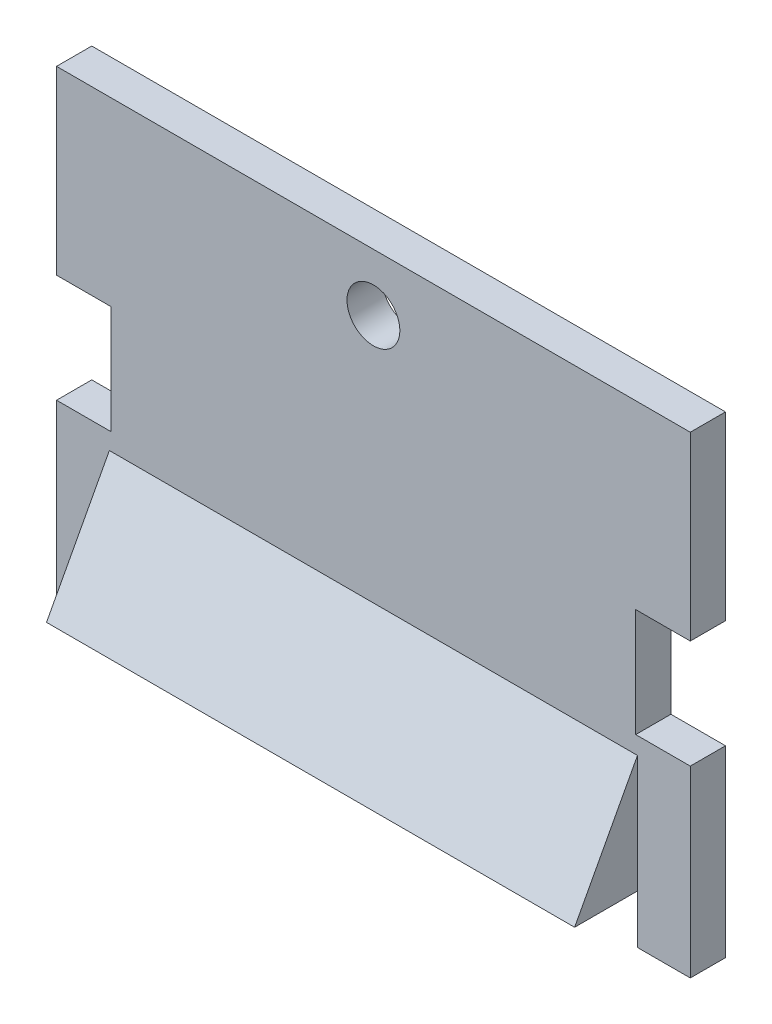
SolidWorks part; units mm, degrees
ref_plane "Front Plane" through (0, 0, 0) normal (0, 0, 1) x (1, 0, 0)
ref_plane "Top Plane" through (0, 0, 0) normal (0, 1, 0) x (1, 0, 0)
ref_plane "Right Plane" through (0, 0, 0) normal (1, 0, 0) x (0, 0, -1)
sketch "Sketch1" plane through (0, 0, 0) normal (1, 0, 0) x (0, 0, -1)
  line L0 (0, 0) -> (0, 26.85)
  line L1 (0, 26.85) -> (-2, 26.85)
  line L2 (-2, 26.85) -> (-2, 9.45)
  line L3 (-2, 9.45) -> (-5.57, 2.78)
  line L4 (-5.57, 2.78) -> (-2, 2.78)
  line L5 (-2, 2.78) -> (-2, 0)
  line L6 (-2, 0) -> (0, 0)
  dimension "D1" = 2
  dimension "D2" = 26.85
  dimension "D3" = 2.78
  dimension "D4" = 3.57
  dimension "D5" = 17.4
extrude "Boss-Extrude1" add sketch "Sketch1" along normal mid plane 36
sketch "Sketch2" plane through (0, 0, 0) normal (0, 0, -1) x (-1, 0, 0)
  line L0 (-18, 0) -> (18, 0) construction
  line L1 (-15, 0) -> (15, 0)
  line L2 (-15, 0) -> (-15, 2.78)
  line L3 (-15, 2.78) -> (15, 2.78)
  line L4 (15, 0) -> (15, 2.78)
  line L5 (-18, 2.78) -> (18, 2.78) construction
  line L6 (-18, 26.85) -> (18, 26.85) construction
  circle A0 centre (0, 23.6) radius 1.5
  point P6 (0, 2.78)
  dimension "D2" = 3
  dimension "D1" = 30
  dimension "D3" = 3.25
extrude "Cut-Extrude1" cut sketch "Sketch2" against normal through all
sketch "Sketch3" plane through (0, 0, 0) normal (0, 0, -1) x (-1, 0, 0)
  line L0 (-18, 0) -> (-18, 26.85) construction
  line L1 (-18, 16.575) -> (-14.9, 16.575)
  line L2 (-18, 16.575) -> (-18, 10.425)
  line L3 (-18, 10.425) -> (-14.9, 10.425)
  line L4 (-14.9, 16.575) -> (-14.9, 10.425)
  line L5 (18, 0) -> (18, 26.85) construction
  line L6 (18, 16.575) -> (14.9, 16.575)
  line L7 (18, 16.575) -> (18, 10.425)
  line L8 (18, 10.425) -> (14.9, 10.425)
  line L9 (14.9, 16.575) -> (14.9, 10.425)
  line L11 (-18, 0) -> (-15, 0) construction
  point P12 (-18, 13.5)
  dimension "D1" = 3.1
  dimension "D2" = 6.15
  dimension "D3" = 13.5
extrude "Cut-Extrude2" cut sketch "Sketch3" against normal through all
sketch "Sketch4" plane through (0, 0, 2) normal (0, 0, 1) x (1, 0, 0)
  line L0 (18, 2.78) -> (-18, 2.78) construction
  line L1 (-18, 10.425) -> (-15, 10.425)
  line L2 (-18, 10.425) -> (-18, 2.78)
  line L3 (-18, 2.78) -> (-15, 2.78)
  line L4 (-15, 10.425) -> (-15, 2.78)
  line L6 (18, 10.425) -> (15, 10.425)
  line L7 (18, 10.425) -> (18, 2.78)
  line L8 (18, 2.78) -> (15, 2.78)
  line L9 (15, 10.425) -> (15, 2.78)
  point P12 (0, 0)
  point P13 (-18, 9.5)
  dimension "D1" = 30
extrude "Cut-Extrude3" cut sketch "Sketch4" along normal through all
